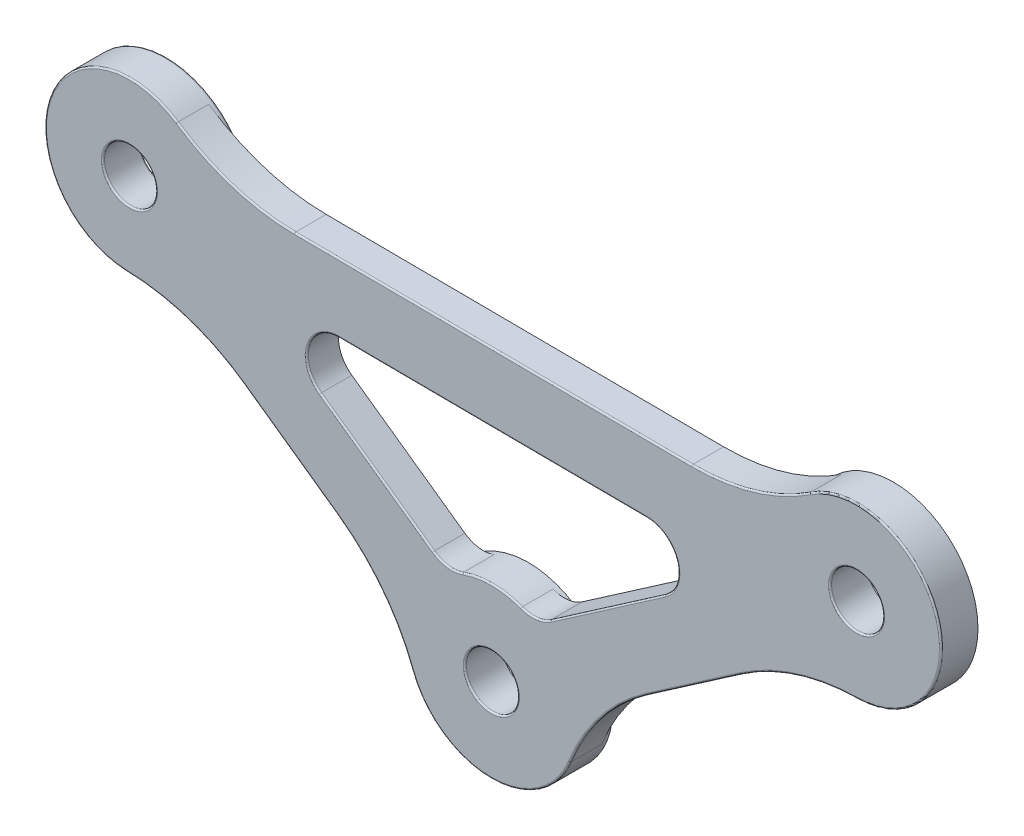
SolidWorks part; units mm, degrees
ref_plane "前视基准面" through (0, 0, 0) normal (0, 0, 1) x (1, 0, 0)
ref_plane "上视基准面" through (0, 0, 0) normal (0, 1, 0) x (1, 0, 0)
ref_plane "右视基准面" through (0, 0, 0) normal (1, 0, 0) x (0, 0, -1)
sketch "草图1" plane through (0, 0, 0) normal (0, 0, 1) x (1, 0, 0)
  line L0 (-67.2252, 197.9171) -> (-101.4725, 222.2302) construction
  line L1 (-32.6652, 221.7835) -> (-67.2252, 197.9171) construction
  line L2 (-101.4725, 222.2302) -> (-32.6652, 221.7835) construction
  line L3 (-67.2252, 197.9171) -> (-101.4725, 222.2302) construction
  line L4 (-32.6652, 221.7835) -> (-67.2252, 197.9171) construction
  line L5 (-101.4725, 222.2302) -> (-32.6652, 221.7835) construction
  circle A0 centre (-101.4725, 222.2302) radius 8
  circle A1 centre (-32.6652, 221.7835) radius 8
  circle A2 centre (-67.2252, 197.9171) radius 8
  circle A3 centre (-101.4725, 222.2302) radius 2.5
  circle A4 centre (-67.2252, 197.9171) radius 2.5
  circle A5 centre (-32.6652, 221.7835) radius 2.5
  dimension "D1" = 16
  dimension "D2" = 5
  dimension "D3" = 5
extrude "凸台-拉伸1" add sketch "草图1" against normal blind 3.5
sketch "草图2" plane through (0, 0, 0) normal (0, 0, 1) x (1, 0, 0)
  line L0 (-94.5688, 222.1854) -> (-39.5688, 221.8283)
  line L1 (-101.4725, 222.2302) -> (-32.6652, 221.7835) construction
  line L2 (-37.6023, 218.374) -> (-62.2881, 201.3266)
  line L3 (-32.6652, 221.7835) -> (-67.2252, 197.9171) construction
  line L4 (-96.58, 218.7569) -> (-72.1177, 201.3904)
  line L5 (-67.2252, 197.9171) -> (-101.4725, 222.2302) construction
  point P19 (-67.0688, 222.0068)
  point P20 (-67.0688, 222.0068)
  point P21 (-49.9452, 209.8503)
  point P22 (-49.9452, 209.8503)
  point P24 (-84.3489, 210.0737)
  dimension "D1" = 55
  dimension "D2" = 30
extrude "拉伸-薄壁1" add sketch "草图2" against normal blind 3 thin thin type mid plane wall 6.5
fillet "圆角1" radius 3 4 edges at (-91.1861, 218.9133, -1.5) (-42.9937, 218.6004, -1.5) (-63.0568, 204.7453, -1.5) (-71.3046, 204.7989, -1.5)
fillet "圆角2" radius 20 6 edges at (-39.954, 225.0808, -1.5) (-94.1414, 225.4327, -1.5) (-97.3931, 215.3484, -1.5) (-75.0673, 199.4987, -1.5) (-59.3632, 199.3968, -1.5) (-36.8335, 214.9552, -1.5)
fillet "圆角3" radius 0.15 25 edges at (-98.9725, 222.2302, -3.5) (-93.4725, 222.2302, -3.5) (-64.7252, 197.9171, 0) (-30.1652, 221.7835, 0) (-98.9725, 222.2302, 0) (-71.3894, 205.2804, 0) (-67.1733, 205.917, 0) (-62.9658, 205.2257, 0) (-56.2233, 209.4644, 0) (-49.6608, 216.5458, 0) (-67.0899, 218.7569, 0) (-84.5462, 216.7723, 0) (-78.0763, 209.6063, 0) (-42.4159, 225.9639, 0) (-25.02, 224.1395, 0) (-38.3713, 212.8396, 0) (-48.0984, 207.176, 0) (-56.8401, 200.0855, 0) (-67.2772, 189.9173, 0) (-77.5813, 200.2202, 0) (-86.2302, 207.4236, 0) (-95.8829, 213.213, 0) (-109.0864, 224.6853, 0) (-91.6683, 226.2836, 0) (-67.0477, 225.2568, 0)
